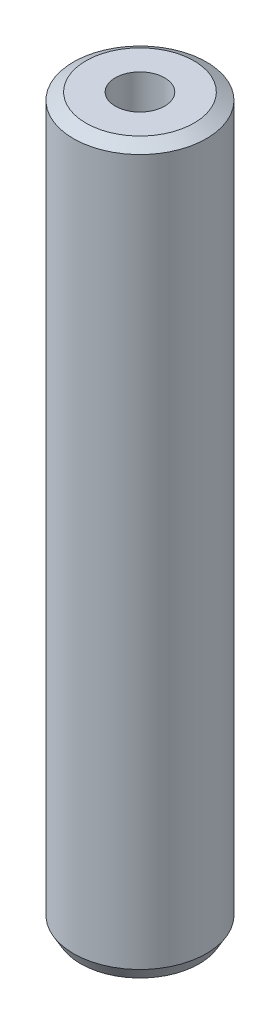
SolidWorks part; units mm, degrees
ref_plane "Front Plane" through (0, 0, 0) normal (0, 0, 1) x (1, 0, 0)
ref_plane "Top Plane" through (0, 0, 0) normal (0, 1, 0) x (1, 0, 0)
ref_plane "Right Plane" through (0, 0, 0) normal (1, 0, 0) x (0, 0, -1)
sketch "Sketch1" plane through (0, 0, 0) normal (0, 1, 0) x (1, 0, 0)
  circle A0 centre (0, 0) radius 55
  dimension "SHAFT_OD" = 110
extrude "Boss-Extrude1" add sketch "Sketch1" along normal blind 600
sketch "Sketch2" plane through (0, 0, 0) normal (0, 1, 0) x (1, 0, 0)
  circle A0 centre (0, 0) radius 20.3794
  dimension "BORE_D" = 40.7589
extrude "Cut-Extrude1" cut sketch "Sketch2" along normal through all
chamfer "Chamfer1" distance 5.9618 angle 60 2 edges at (0, 600, 55) (0, 0, 55) first distance on face at (0, 600, 55) first distance on face at (0, 0, 20.3794)
